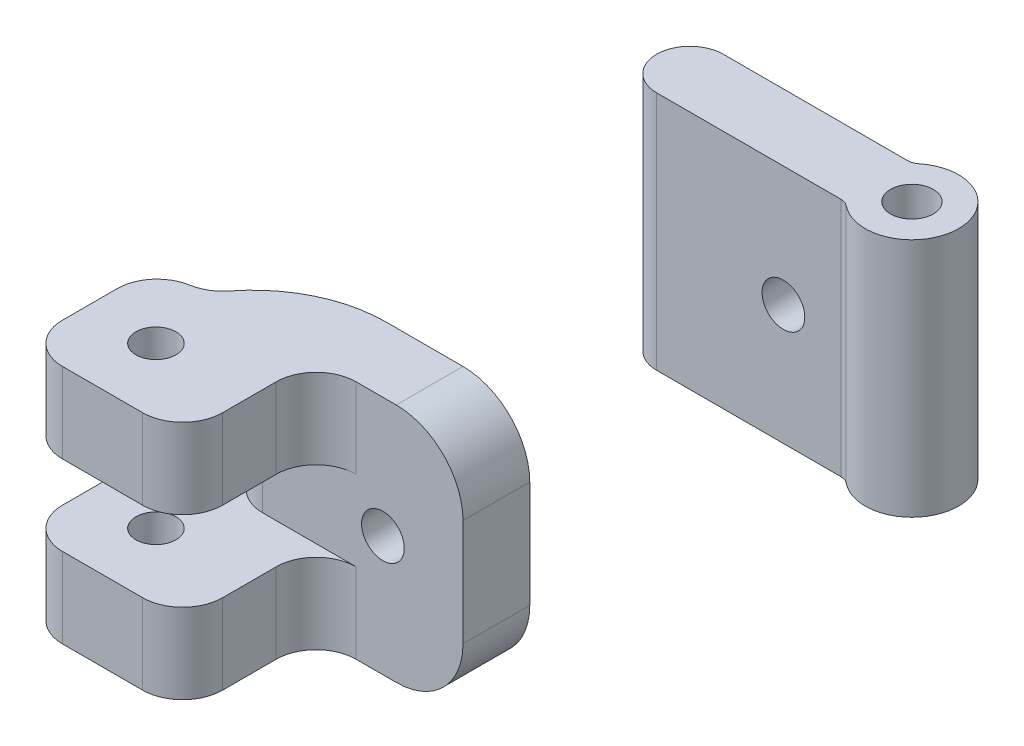
SolidWorks part; units mm, degrees
ref_plane "Front Plane" through (0, 0, 0) normal (0, 0, 1) x (1, 0, 0)
ref_plane "Top Plane" through (0, 0, 0) normal (0, 1, 0) x (1, 0, 0)
ref_plane "Right Plane" through (0, 0, 0) normal (1, 0, 0) x (0, 0, -1)
sketch "Sketch1" plane through (0, 0, 0) normal (0, 0, 1) x (1, 0, 0)
  line L2 (-10.125, 9) -> (10.125, 9)
  line L3 (-10.125, 9) -> (-10.125, -9)
  line L4 (-10.125, -9) -> (10.125, -9)
  line L5 (10.125, 9) -> (10.125, -9)
  line L6 (-10.125, 9) -> (10.125, -9) construction
  line L7 (-10.125, -9) -> (10.125, 9) construction
  point P2 (0, 0)
  dimension "D1" = 20.25
  dimension "D2" = 18
extrude "Boss-Extrude1" add sketch "Sketch1" along normal blind 5
sketch "Sketch2" plane through (0, 0, 5) normal (0, 0, 1) x (1, 0, 0)
  line L0 (-10.125, -9) -> (10.125, -9) construction
  line L1 (-10.125, 9) -> (-5.125, 9)
  line L2 (-10.125, 9) -> (-10.125, -9)
  line L3 (-10.125, -9) -> (-5.125, -9)
  line L4 (-5.125, 9) -> (-5.125, -9)
  dimension "D1" = 5
extrude "Boss-Extrude2" add sketch "Sketch2" along normal blind 25
sketch "Sketch3" plane through (0, 0, 30) normal (0, 0, 1) x (1, 0, 0)
  line L1 (-10.125, 9) -> (7.875, 9)
  line L2 (-10.125, 9) -> (-10.125, -9)
  line L3 (-10.125, -9) -> (7.875, -9)
  line L4 (7.875, 9) -> (7.875, -9)
  dimension "D1" = 18
  dimension "D2" = 18
  dimension "D3" = 18
extrude "Boss-Extrude3" add sketch "Sketch3" along normal blind 5
sketch "Sketch5" plane through (0, 0, 30) normal (0, 0, -1) x (-1, 0, 0)
  line L0 (-7.875, 0) -> (8.5, 0) construction
  line L1 (-7.875, -9) -> (-7.875, 9) construction
  line L3 (10.125, 9) -> (10.125, -9) construction
  circle A0 centre (-1.875, 0) radius 1.6
  dimension "D1" = 3.2
  dimension "D2" = 12
extrude "Cut-Extrude2" cut sketch "Sketch5" against normal through all both and the other way through all
fillet "Fillet7" radius 5 2 edges at (7.875, -9, 32.5) (7.875, 9, 32.5)
sketch "Sketch10" plane through (0, -9, 0) normal (0, -1, 0) x (1, 0, 0)
  line L0 (10.125, 2.5) -> (6, 2.5) construction
  line L1 (10.125, 5) -> (10.125, 0) construction
  circle A0 centre (9, 2.5) radius 1.6
  circle A1 centre (9, 2.5) radius 3.5
  dimension "D1" = 3.2
  dimension "D3" = 7
extrude "Cut-Extrude4" cut sketch "Sketch10" against normal through all both and the other way through all contours A0
extrude "Boss-Extrude7" add sketch "Sketch10<4>" against normal blind 18 contours A1 | A0
sketch "Sketch10<4>" plane through (0, -9, 0) normal (0, -1, 0) x (1, 0, 0) same geometry as "Sketch10"
fillet "Fillet13" radius 1 2 edges at (6.5505, 0, 0) (6.5505, 0, 5)
sketch "Sketch11" plane through (0, 0, 35) normal (0, 0, 1) x (1, 0, 0)
  line L0 (-10.125, 9) -> (-10.125, -9) construction
  line L1 (-10.125, -9) -> (2.875, -9) construction
  line L2 (-15.125, 3) -> (-3.125, 3)
  line L7 (-15.125, 9) -> (-3.125, 3) construction
  line L8 (-3.125, 9) -> (-15.125, 3) construction
  line L9 (2.875, 9) -> (-10.125, 9) construction
  line L10 (-15.125, -3) -> (-3.125, -9) construction
  line L11 (-15.125, 3) -> (-15.125, 9)
  line L12 (-15.125, 9) -> (-3.125, 9)
  line L13 (-3.125, 3) -> (-3.125, 9)
  line L14 (-15.125, -3) -> (-3.125, -3)
  line L15 (-15.125, -3) -> (-15.125, -9)
  line L16 (-15.125, -9) -> (-3.125, -9)
  line L17 (-3.125, -3) -> (-3.125, -9)
  line L18 (-3.125, -3) -> (-15.125, -9) construction
  point P4 (-10.125, 3.25)
  dimension "D3" = 12
  dimension "D1" = 5.75
  dimension "D2" = 0
  dimension "D4" = 12
  dimension "D5" = 6
  dimension "D6" = 5
  dimension "D7" = 5
extrude "Boss-Extrude8" add sketch "Sketch11" along normal blind 10 contours L11 L2 L13 L12 | L15 L14 L17 L16
sketch "Sketch12" plane through (0, 9, 0) normal (0, 1, 0) x (1, 0, 0)
  line L0 (-15.125, -35) -> (-10.125, -35) construction
  line L1 (-15.125, -45) -> (-15.125, -35) construction
  circle A0 centre (-10.125, -40) radius 1.5
  dimension "D1" = 3
  dimension "D2" = 5
  dimension "D3" = 5
extrude "Cut-Extrude5" cut sketch "Sketch12" along normal through all and the other way through all contours A0
fillet "Fillet17" radius 3 8 edges at (-3.125, 6, 35) (-3.125, 6, 45) (-15.125, 6, 45) (-10.125, 6, 35) (-3.125, -6, 35) (-3.125, -6, 45) (-15.125, -6, 45) (-10.125, -6, 35)
fillet "Fillet18" radius 3 2 edges at (-15.125, 6, 35) (-15.125, -6, 35)
fillet "Fillet19" radius 3 1 edges at (-10.125, 0, 35)
sketch "Sketch13" plane through (-5.125, 0, 0) normal (1, 0, 0) x (0, 0, -1)
  line L1 (-30, 9) -> (-5, 9)
  line L2 (-30, 9) -> (-30, -9)
  line L3 (-30, -9) -> (-5, -9)
  line L4 (-5, 9) -> (-5, -9)
extrude "Cut-Extrude6" cut sketch "Sketch13" against normal blind 10
fillet "Fillet20" radius 10 1 edges at (-10.125, 0, 30)
fillet "Fillet21" radius 2.5 2 edges at (-10.125, 0, 0) (-10.125, 0, 5)
